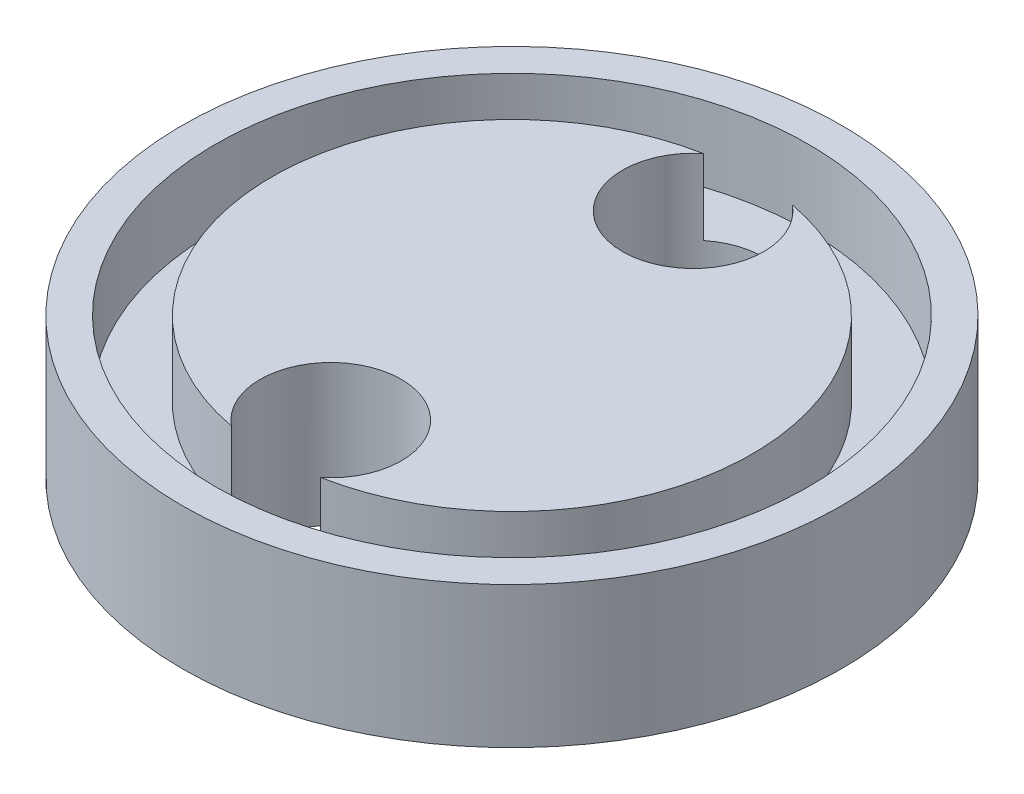
SolidWorks part; units mm, degrees
ref_plane "Front Plane" through (0, 0, 0) normal (0, 0, 1) x (1, 0, 0)
ref_plane "Top Plane" through (0, 0, 0) normal (0, 1, 0) x (1, 0, 0)
ref_plane "Right Plane" through (0, 0, 0) normal (1, 0, 0) x (0, 0, -1)
sketch "Sketch4" plane through (0, 0, 0) normal (0, 1, 0) x (1, 0, 0)
  line L0 (0, 0) -> (0, 13.5) construction
  line L1 (0, 0) -> (0, -13.5) construction
  circle A1 centre (0, 0) radius 17.5
  circle A2 centre (0, 9.6208) radius 3.75
  circle A3 centre (0, -9.6208) radius 3.75
  circle A4 centre (0, 9.6208) radius 2.5 construction
  circle A5 centre (0, -9.6208) radius 2.5 construction
  point P9 (0, 6.75)
  point P10 (1.171, 7.9223)
  point P11 (0, 0)
  point P14 (0, 0)
  point P15 (0, 0)
  point P16 (1.3496, -8.5975)
  point P17 (0, 0)
  dimension "D1" = 13.5
  dimension "D2" = 35
  dimension "D4" = 7.5
  dimension "D5" = 7.5
  dimension "D3" = 13.5
extrude "LidBase" add sketch "Sketch4" along normal blind 7.5
sketch "Sketch5" plane through (0, 7.5, 0) normal (0, 1, 0) x (1, 0, 0)
  circle A0 centre (0, 0) radius 12.75
  circle A1 centre (0, 0) radius 15.75
  dimension "D1" = 31.5
  dimension "D2" = 25.5
extrude "LidGrooves" cut sketch "Sketch5" against normal blind 4
